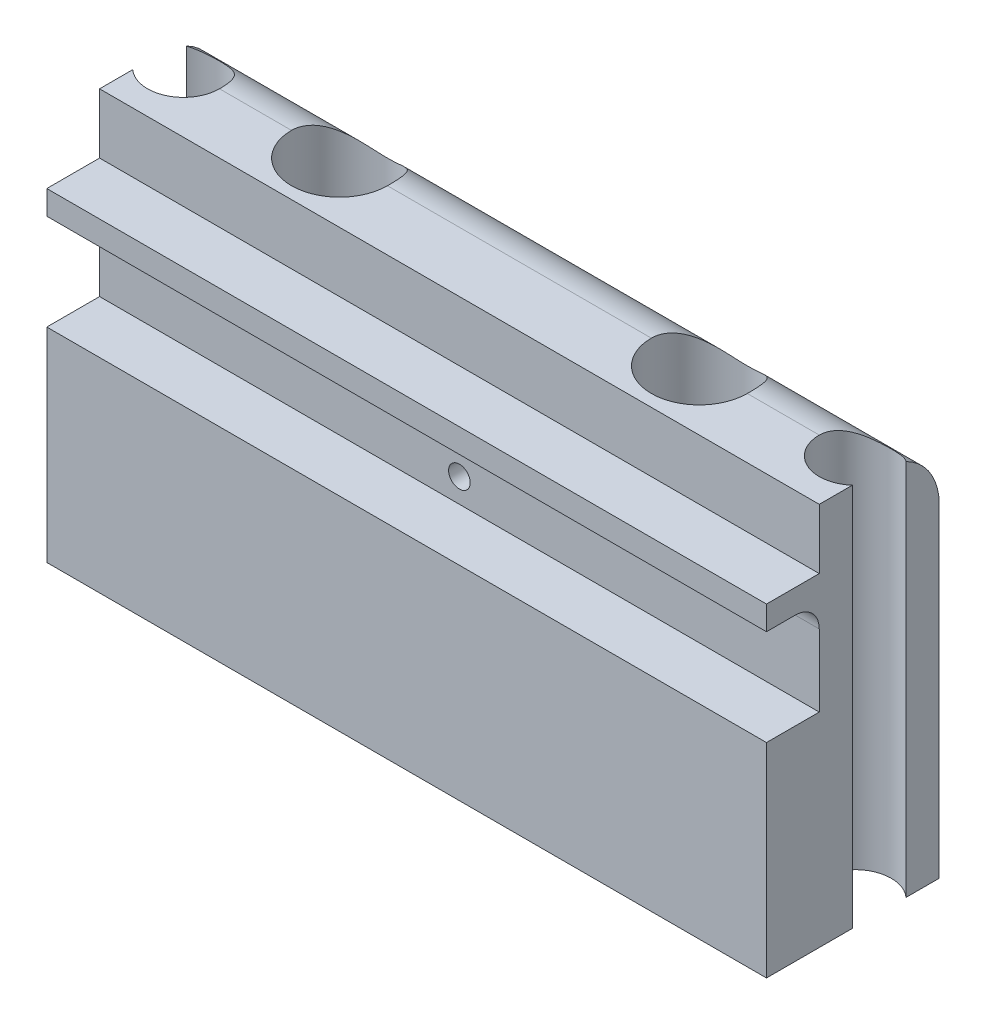
SolidWorks part; units mm, degrees
ref_plane "Front Plane" through (0, 0, 0) normal (0, 0, 1) x (1, 0, 0)
ref_plane "Top Plane" through (0, 0, 0) normal (0, 1, 0) x (1, 0, 0)
ref_plane "Right Plane" through (0, 0, 0) normal (1, 0, 0) x (0, 0, -1)
sketch "Sketch2" plane through (0, 0, 0) normal (1, 0, 0) x (0, 0, -1)
  line L1 (0, 0) -> (18.288, 0)
  line L2 (0, 0) -> (0, 40.64)
  line L3 (0, 40.64) -> (18.288, 40.64)
  line L4 (18.288, 0) -> (18.288, 40.64)
  dimension "D1" = 18.288
  dimension "D2" = 40.64
extrude "Boss-Extrude1" add sketch "Sketch2" along normal blind 76.2
sketch "Sketch3" plane through (0, 0, 0) normal (-1, 0, 0) x (0, 0, 1)
  line L0 (-18.288, 0) -> (-18.288, 40.64) construction
  line L1 (0, 40.64) -> (-5.588, 40.64)
  line L2 (0, 40.64) -> (0, 34.29)
  line L3 (0, 34.29) -> (-5.588, 34.29)
  line L4 (-5.588, 40.64) -> (-5.588, 34.29)
  line L5 (0, 40.64) -> (0, 0) construction
  line L6 (0, 31.75) -> (-5.588, 31.75)
  line L7 (0, 31.75) -> (0, 21.59)
  line L8 (0, 21.59) -> (-5.588, 21.59)
  line L9 (-5.588, 31.75) -> (-5.588, 21.59)
  dimension "D1" = 6.35
  dimension "D2" = 12.7
  dimension "D3" = 2.54
  dimension "D4" = 10.16
  dimension "D5" = 12.7
extrude "Cut-Extrude1" cut sketch "Sketch3" against normal up to next
sketch "Sketch4" plane through (0, 0, -5.588) normal (0, 0, 1) x (1, 0, 0)
  line L0 (0, 31.75) -> (0, 21.59) construction
  line L1 (76.2, 21.59) -> (0, 21.59) construction
  circle A0 centre (38.1, 24.13) radius 1.143
  dimension "D1" = 2.286
  dimension "D2" = 38.1
  dimension "D3" = 2.54
extrude "Cut-Extrude2" cut sketch "Sketch4" against normal up to next
sketch "Sketch5" plane through (0, 40.64, 0) normal (0, 1, 0) x (1, 0, 0)
  line L0 (38.1, 18.288) -> (38.1, 5.588) construction
  line L1 (76.2, 18.288) -> (0, 18.288) construction
  line L2 (76.2, 5.588) -> (0, 5.588) construction
  line L3 (76.2, 11.938) -> (0, 11.938) construction
  line L4 (76.2, 18.288) -> (76.2, 5.588) construction
  line L5 (0, 18.288) -> (0, 5.588) construction
  circle A0 centre (57.15, 11.938) radius 2.032
  circle A1 centre (19.05, 11.938) radius 2.032
  dimension "D1" = 4.064
  dimension "D2" = 4.064
  dimension "D3" = 19.05
  dimension "D4" = 19.05
extrude "Cut-Extrude3" cut sketch "Sketch5" against normal up to next
sketch "Sketch6" plane through (0, 40.64, 0) normal (0, 1, 0) x (1, 0, 0)
  circle A0 centre (19.05, 11.938) radius 5.08
  circle A1 centre (57.15, 11.938) radius 5.08
  dimension "D1" = 10.16
  dimension "D2" = 10.16
extrude "Cut-Extrude4" cut sketch "Sketch6" against normal offset from surface (15.24 mm away) 25.4 up to face at (57.15, 0, -9.906)
fillet "Fillet1" radius 6.35 1 edges at (38.1, 40.64, -18.288)
fillet "Fillet2" radius 2.54 1 edges at (38.1, 31.75, -5.588)
sketch "Sketch7" plane through (0, 0, 0) normal (0, -1, 0) x (1, 0, 0)
  line L0 (0, -11.938) -> (76.2, -11.938) construction
  line L1 (0, 0) -> (0, -18.288) construction
  line L2 (76.2, 0) -> (76.2, -18.288) construction
  line L3 (76.2, -18.288) -> (0, -18.288) construction
  circle A0 centre (2.54, -11.938) radius 3.81
  circle A1 centre (73.66, -11.938) radius 3.81
  dimension "D3" = 7.62
  dimension "D4" = 7.62
  dimension "D1" = 6.35
  dimension "D2" = 2.54
  dimension "D5" = 2.54
extrude "Cut-Extrude5" cut sketch "Sketch7" against normal through all
